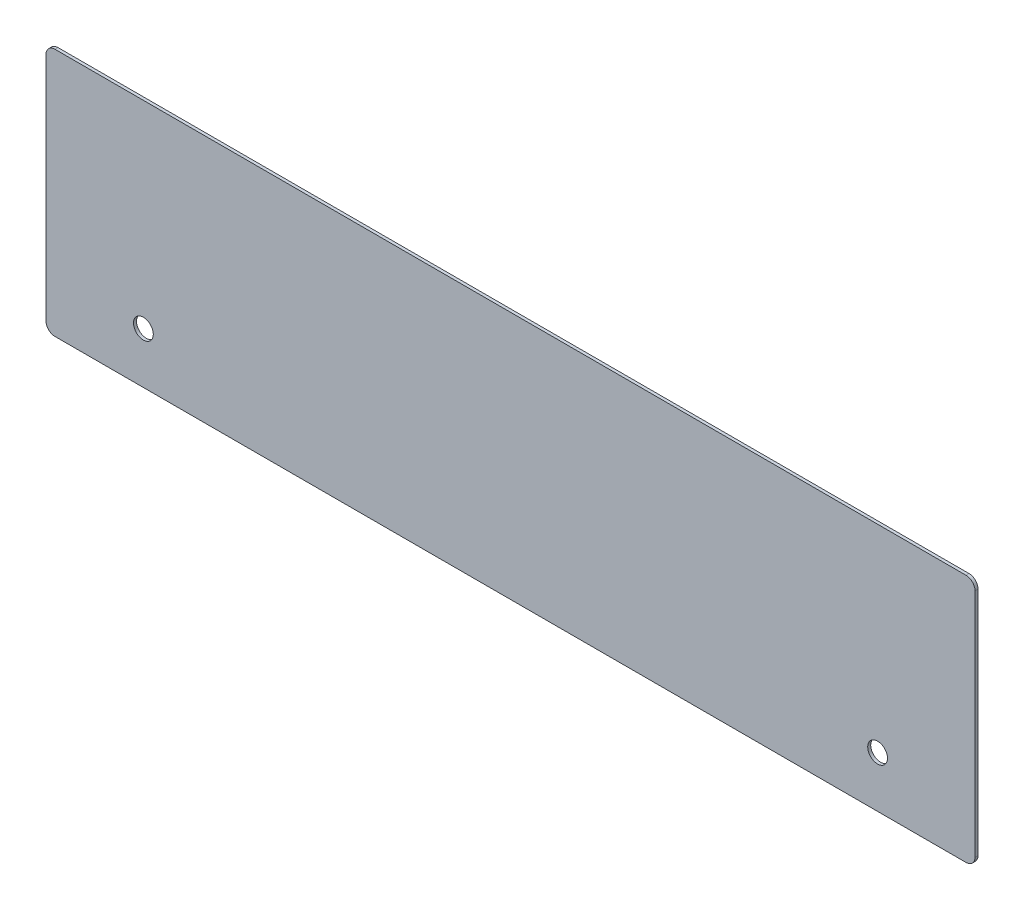
SolidWorks part; units mm, degrees
ref_plane "Front Plane" through (0, 0, 0) normal (0, 0, 1) x (1, 0, 0)
ref_plane "Top Plane" through (0, 0, 0) normal (0, 1, 0) x (1, 0, 0)
ref_plane "Right Plane" through (0, 0, 0) normal (1, 0, 0) x (0, 0, -1)
sketch "Sketch1" plane through (0, 0, 0) normal (0, 0, 1) x (1, 0, 0)
  line L1 (-155, -41.5) -> (155, -41.5)
  line L2 (-155, -41.5) -> (-155, 41.5)
  line L3 (-155, 41.5) -> (155, 41.5)
  line L4 (155, -41.5) -> (155, 41.5)
  line L5 (-155, -41.5) -> (155, 41.5) construction
  line L6 (-155, 41.5) -> (155, -41.5) construction
  point P0 (0, 0)
  dimension "D1" = 83
  dimension "D2" = 310
base flange "Base-Flange1" sketch "Sketch1" thickness 1 reverse thickness direction no parameters "D1"=0.7366
fillet "Fillet1" radius 3 4 edges at (-155, 41.5, -0.5) (-155, -41.5, -0.5) (155, -41.5, -0.5) (155, 41.5, -0.5)
sketch "Sketch6" plane through (0, 0, 0) normal (0, 0, 1) x (1, 0, 0)
  circle A0 centre (122.5, -24.4934) radius 3.3
  circle A1 centre (-122.5, -24.4934) radius 3.3
  dimension "D1" = 6.6
  dimension "D2" = 6.6
extrude "Cut-Extrude1" cut sketch "Sketch6" against normal blind 10 normal cut yes
sketch "Bend-Lines1" [suppressed] plane through (0, 0, 0) normal (0, 1, 0) x (1, 0, 0)
sketch "Bounding-Box1" [suppressed] plane through (0, 0, 0) normal (0, 1, 0) x (1, 0, 0)
sheet metal parameters "Sheet-Metal1" thickness 1 parameters "D1"=0.7366
flat pattern "Flat-Pattern1" [suppressed]
sketch "Bend-Lines2" plane through (0, 0, 0) normal (0, 1, 0) x (1, 0, 0)
sketch3d "Bounding-Box2" [suppressed]
  line L0 (-150, 41.5, 0) -> (150, 41.5, 0) construction
  line L1 (-150, -41.5, 0) -> (150, -41.5, 0) construction
  line L2 (-150, 41.5, 0) -> (-150, -41.5, 0) construction
  line L3 (150, 41.5, 0) -> (150, -41.5, 0) construction
sheet metal parameters "Sheet-Metal2" thickness 1 parameters "D1"=0.7366
flat pattern "Flat-Pattern1"
sketch "Bend-Lines2" plane through (0, 0, 0) normal (0, 1, 0) x (1, 0, 0)
sketch3d "Bounding-Box2" [suppressed]
  line L0 (-155, 41.5, 0) -> (155, 41.5, 0) construction
  line L1 (-155, -41.5, 0) -> (155, -41.5, 0) construction
  line L2 (-155, 41.5, 0) -> (-155, -41.5, 0) construction
  line L3 (155, 41.5, 0) -> (155, -41.5, 0) construction
